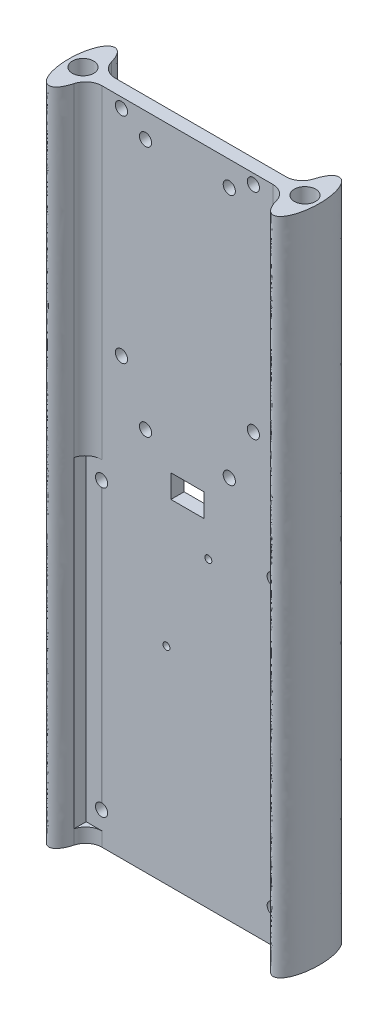
SolidWorks part; units mm, degrees
note: The reader was unsure of these and kept them because the rebuilt part matched: shared geometry of "Sketch2<3>".
ref_plane "Front Plane" through (0, 0, 0) normal (0, 0, 1) x (1, 0, 0)
ref_plane "Top Plane" through (0, 0, 0) normal (0, 1, 0) x (1, 0, 0)
ref_plane "Right Plane" through (0, 0, 0) normal (1, 0, 0) x (0, 0, -1)
sketch "Sketch1" plane through (0, 0, 0) normal (0, 1, 0) x (1, 0, 0)
  line L0 (0, 0) -> (0, -2) construction
  line L1 (34, 2) -> (-34, 2)
  line L2 (34, 2) -> (34, -2)
  line L3 (34, -2) -> (-34, -2)
  line L4 (-34, 2) -> (-34, -2)
  line L5 (34, 2) -> (-34, -2) construction
  line L6 (34, -2) -> (-34, 2) construction
  circle A2 centre (-33.655, 0) radius 3.2385
  circle A3 centre (33.655, 0) radius 3.2385
  ellipse E0 centre (-34, 0) end of major axis (-34, -10) minor radius 4
  ellipse E1 centre (34, 0) end of major axis (34, -10) minor radius 4
  point P0 (0, 0)
  dimension "D5" = 6.477
  dimension "D1" = 76
  dimension "D2" = 8
  dimension "D3" = 4
  dimension "D4" = 20
  dimension "D6" = 67.31
extrude "Boss-Extrude1" add sketch "Sketch1" along normal blind 200
fillet "Fillet1" radius 5 4 edges at (30.0808, 100, -2) (30.0808, 100, 2) (-30.0808, 100, -2) (-30.0808, 100, 2)
sketch "Sketch2" plane through (0, 0, 2) normal (0, 0, 1) x (1, 0, 0)
  line L0 (25.8853, 200) -> (-25.8853, 200) construction
  line L1 (-12.7, 192.5) -> (12.7, 192.5)
  line L2 (-12.7, 192.5) -> (-12.7, 116.3)
  line L3 (-12.7, 116.3) -> (12.7, 116.3)
  line L4 (12.7, 192.5) -> (12.7, 116.3)
  line L5 (-12.7, 192.5) -> (12.7, 116.3) construction
  line L6 (-12.7, 116.3) -> (12.7, 192.5) construction
  line L7 (0, 154.4) -> (0, 200) construction
  line L8 (0, 105.05) -> (0, 116.3) construction
  line L9 (5, 108.8) -> (-5, 108.8)
  line L10 (5, 108.8) -> (5, 101.3)
  line L11 (5, 101.3) -> (-5, 101.3)
  line L12 (-5, 108.8) -> (-5, 101.3)
  line L13 (5, 108.8) -> (-5, 101.3) construction
  line L14 (5, 101.3) -> (-5, 108.8) construction
  line L15 (0, 53.05) -> (0, 0) construction
  line L16 (26.03, 9.8) -> (-26.03, 9.8)
  line L17 (26.03, 9.8) -> (26.03, 96.3)
  line L18 (26.03, 96.3) -> (-26.03, 96.3)
  line L19 (-26.03, 9.8) -> (-26.03, 96.3)
  line L20 (26.03, 9.8) -> (-26.03, 96.3) construction
  line L21 (26.03, 96.3) -> (-26.03, 9.8) construction
  line L22 (-30.7057, 0) -> (-30.7057, 200) construction
  line L23 (30.7057, 101.8) -> (-30.7057, 101.8)
  line L24 (30.7057, 101.8) -> (30.7057, 4.3)
  line L25 (30.7057, 4.3) -> (-30.7057, 4.3)
  line L26 (-30.7057, 101.8) -> (-30.7057, 4.3)
  line L27 (30.7057, 101.8) -> (-30.7057, 4.3) construction
  line L28 (30.7057, 4.3) -> (-30.7057, 101.8) construction
  circle A0 centre (-12.7, 192.5) radius 1.85
  circle A1 centre (12.7, 192.5) radius 1.85
  circle A2 centre (-12.7, 116.3) radius 1.85
  circle A3 centre (12.7, 116.3) radius 1.85
  circle A4 centre (26.03, 96.3) radius 1.85
  circle A5 centre (-26.03, 96.3) radius 1.85
  circle A6 centre (-26.03, 9.8) radius 1.85
  circle A7 centre (26.03, 9.8) radius 1.85
  point P0 (0, 154.4)
  point P9 (0, 105.05)
  point P16 (0, 53.05)
  point P24 (0, 96.3)
  line M11 (25.8853, 0) -> (25.8853, 200)
  line M13 (-25.8853, 200) -> (-25.8853, 0)
  dimension "D10" = 3.7
  dimension "D1" = 7.5
  dimension "D2" = 25.4
  dimension "D3" = 76.2
  dimension "D4" = 10
  dimension "D5" = 7.5
  dimension "D6" = 7.5
  dimension "D7" = 52.06
  dimension "D8" = 86.5
  dimension "D9" = 5
  dimension "D11" = 97.5
sketch "Sketch3" plane through (0, 0, -2) normal (0, 0, -1) x (-1, 0, 0)
  line L0 (0, 164.5) -> (0, 0) construction
  line L1 (20, 132) -> (-20, 132)
  line L2 (20, 132) -> (20, 197)
  line L3 (20, 197) -> (-20, 197)
  line L4 (-20, 132) -> (-20, 197)
  line L5 (20, 132) -> (-20, 197) construction
  line L6 (20, 197) -> (-20, 132) construction
  line L7 (-25.8853, 200) -> (25.8853, 200) construction
  circle A0 centre (-20, 197) radius 1.85
  circle A1 centre (20, 197) radius 1.85
  circle A2 centre (20, 132) radius 1.85
  circle A3 centre (-20, 132) radius 1.85
  point P0 (0, 164.5)
  dimension "D4" = 3.7
  dimension "D1" = 40
  dimension "D2" = 65
  dimension "D3" = 3
extrude "Cut-Extrude1" cut sketch "Sketch3" against normal through all both and the other way through all contours L3 A0 L4 | L2 A1 L3 | L3 A1 L2 | L4 A0 L3 | L1 A3 L4 | L4 A3 L1 | L2 A2 L1 | L1 A2 L2
extrude "Cut-Extrude2" cut sketch "Sketch2" against normal through all both and the other way through all contours L19 A6 L16 M13 | A6 L19 L16 M13 | L16 A6 M13 | A6 L16 M13 | L17 A7 L16 M11 | A7 L16 M11 | A7 L17 L16 M11 | L16 A7 M11 | A4 L17 L18 M11 | L18 A4 M11 | A4 L18 M11 | L17 A4 L18 M11 | L19 A5 L18 M13 | A5 L18 M13 | L18 A5 M13 | A5 L19 L18 M13 | L9 L12 L11 L10 | L4 A3 L3 | L3 A3 L4 | L2 A2 L3 | L3 A2 L2 | L2 A0 L1 | L1 A0 L2 | L1 A1 L4 | L4 A1 L1
extrude "Cut-Extrude3" cut sketch "Sketch2<3>" along normal blind 30 contours A7 L25 L24 L23 A4 L17 M11 | A6 L19 A5 L23 L26 L25 M13
sketch "Sketch2<3>" plane through (0, 0, 2) normal (0, 0, 1) x (1, 0, 0) same geometry as "Sketch2"
sketch "Sketch4" plane through (0, 0, -2) normal (0, 0, -1) x (-1, 0, 0)
  line L0 (0, 62.59) -> (0, 91.8) construction
  line L1 (0, 91.8) -> (-6.35, 91.8) construction
  line L2 (0, 62.59) -> (6.35, 62.59) construction
  line L4 (-5, 101.8) -> (5, 101.8) construction
  circle A0 centre (-6.35, 91.8) radius 1.05
  circle A1 centre (6.35, 62.59) radius 1.05
  dimension "D5" = 2.1
  dimension "D1" = 29.21
  dimension "D2" = 6.35
  dimension "D3" = 6.35
  dimension "D4" = 10
extrude "Cut-Extrude4" cut sketch "Sketch4" against normal blind 10
